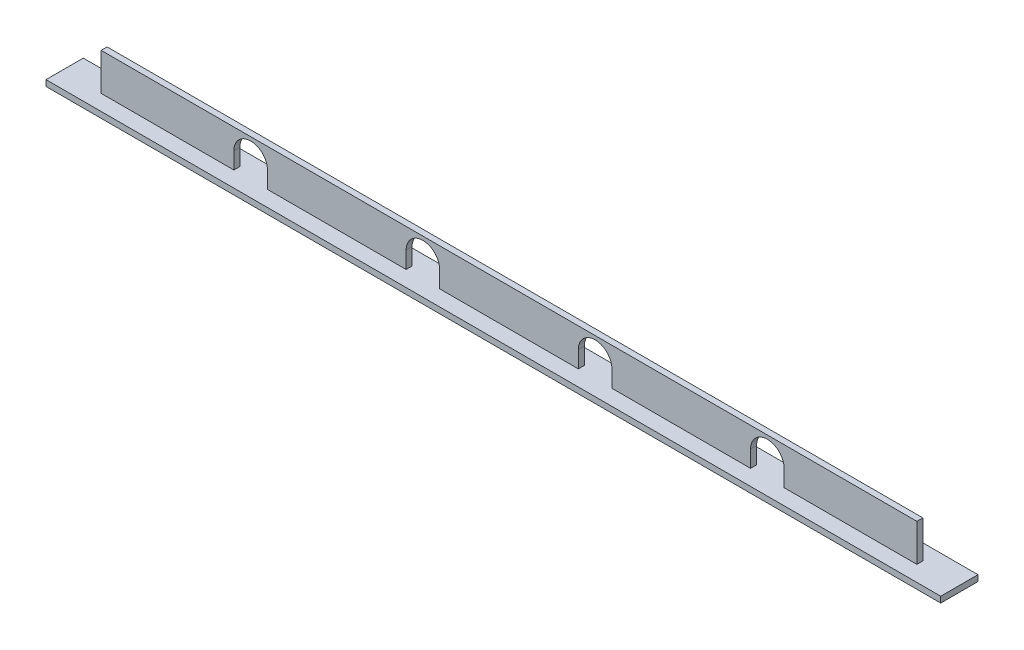
SolidWorks part; units mm, degrees
material "12Х18Н10Т ГОСТ 4543-71"
ref_plane "Спереди" through (0, 0, 0) normal (0, 0, 1) x (1, 0, 0)
ref_plane "Сверху" through (0, 0, 0) normal (0, 1, 0) x (1, 0, 0)
ref_plane "Справа" through (0, 0, 0) normal (1, 0, 0) x (0, 0, -1)
sketch "Эскиз1" plane through (0, 0, 0) normal (0, 0, 1) x (1, 0, 0)
  line L0 (-600, -2.5) -> (-600, -25)
  line L1 (-605, -25) -> (-600, -25)
  line L2 (-605, -25) -> (-605, 25)
  line L3 (-605, 25) -> (605, 25)
  line L4 (605, -25) -> (605, 25)
  line L5 (0, 25) -> (0, -25) construction
  line L6 (-605, 0) -> (605, 0) construction
  line L7 (-555, -2.5) -> (-555, -25)
  line L8 (-555, -25) -> (-369, -25)
  line L9 (-369, -2.5) -> (-369, -25)
  line L10 (-324, -2.5) -> (-324, -25)
  line L11 (-138, -2.5) -> (-138, -25)
  line L12 (-93, -2.5) -> (-93, -25)
  line L13 (93, -2.5) -> (93, -25)
  line L14 (138, -2.5) -> (138, -25)
  line L15 (324, -2.5) -> (324, -25)
  line L16 (369, -2.5) -> (369, -25)
  line L17 (555, -2.5) -> (555, -25)
  line L18 (600, -2.5) -> (600, -25)
  line L19 (-324, -25) -> (-138, -25)
  line L20 (-93, -25) -> (93, -25)
  line L21 (138, -25) -> (324, -25)
  line L22 (369, -25) -> (555, -25)
  line L23 (600, -25) -> (605, -25)
  arc A0 (-555, -2.5) -> (-600, -2.5) centre (-577.5, -2.5) ccw
  arc A1 (-324, -2.5) -> (-369, -2.5) centre (-346.5, -2.5) ccw
  arc A2 (-93, -2.5) -> (-138, -2.5) centre (-115.5, -2.5) ccw
  arc A3 (138, -2.5) -> (93, -2.5) centre (115.5, -2.5) ccw
  arc A4 (369, -2.5) -> (324, -2.5) centre (346.5, -2.5) ccw
  arc A5 (600, -2.5) -> (555, -2.5) centre (577.5, -2.5) ccw
  point P0 (0, 0)
  dimension "D3" = 45
  dimension "D1" = 1210
  dimension "D2" = 50
  dimension "D5" = 5
  dimension "D4" = 6
extrude "Бобышка-Вытянуть1" add sketch "Эскиз1" along normal mid plane 8
sketch "Эскиз3" plane through (0, 25, 0) normal (0, 1, 0) x (1, 0, 0)
  line L0 (0, -208.2618) -> (0, 258.9795) construction
  line L1 (555, -4) -> (555, 4) construction
  line L4 (605, 4) -> (-605, 4)
  line L5 (-605, 4) -> (-605, -4)
  line L6 (-605, -4) -> (605, -4)
  line L7 (605, -4) -> (605, 4)
  line L8 (547, 4) -> (-547, 4)
  line L9 (-547, 4) -> (-547, -4)
  line L10 (-547, -4) -> (547, -4)
  line L11 (547, -4) -> (547, 4)
  point P11 (0, 0)
  dimension "D2" = 8
  dimension "D1" = 0
extrude "Вырез-Вытянуть1" cut sketch "Эскиз3" against normal through all flip side to cut
sketch "Эскиз2" plane through (0, -25, 0) normal (0, -1, 0) x (1, 0, 0)
  line L1 (-600, -25) -> (600, -25)
  line L2 (-600, -25) -> (-600, 25)
  line L3 (-600, 25) -> (600, 25)
  line L4 (600, -25) -> (600, 25)
  line L5 (0, 25) -> (0, -25) construction
  line L6 (-600, 0) -> (600, 0) construction
  point P0 (0, 0)
  point P4 (0, 0)
  dimension "D1" = 50
  dimension "D2" = 1200
extrude "Бобышка-Вытянуть2" add sketch "Эскиз2" along normal blind 8 separate body
equation "\"расстояние между опорами фермы\"= 49"
equation "\"центр боковых направляющих\"= 1210 / 2"
equation "\"толщина полосы\"= 8"
equation "\"ширина полосы\"= 50"
equation "\"ширина боковой направляющей\"= 100 / 2"
equation "\"расстояние между центрами фиксатора\"= 178 / 2"
equation "\"D2@Эскиз3\"=\"толщина полосы\""
